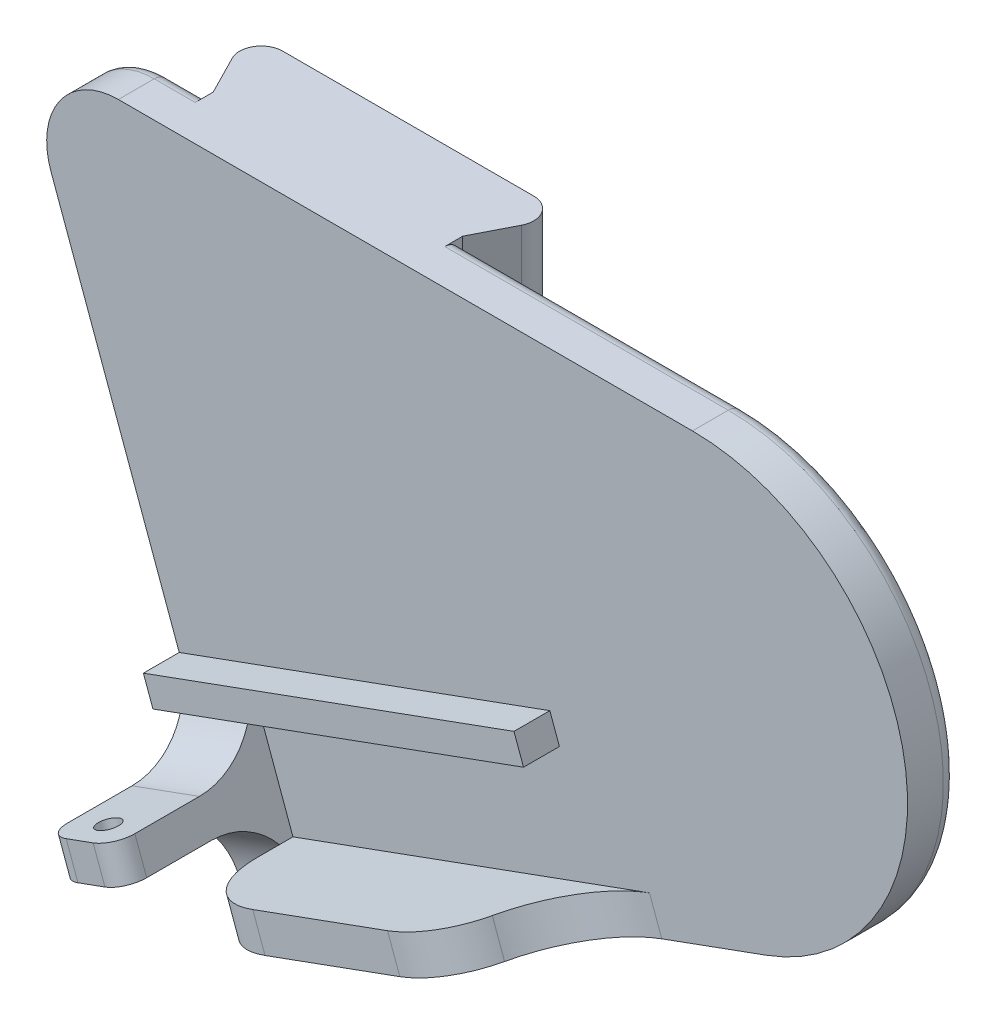
SolidWorks part; units mm, degrees
ref_plane "Alzado" through (0, 0, 0) normal (0, 0, 1) x (1, 0, 0)
ref_plane "Planta" through (0, 0, 0) normal (0, 1, 0) x (1, 0, 0)
ref_plane "Vista lateral" through (0, 0, 0) normal (1, 0, 0) x (0, 0, -1)
sketch "Croquis1" plane through (0, 0, 0) normal (0, 1, 0) x (1, 0, 0)
  line L0 (-20.1738, -4.3634) -> (-17.4, -9.8)
  line L1 (17.4, -9.8) -> (-17.4, -9.8) construction
  line L3 (17.5015, 0) -> (-17.5015, 0)
  line L5 (20.1738, -4.3634) -> (17.4, -9.8)
  line L8 (-17.4, -9.8) -> (-17.4, -10.3)
  line L9 (-17.4, -10.3) -> (17.4, -10.3)
  line L10 (17.4, -9.8) -> (17.4, -10.3)
  arc A0 (20.1738, -4.3634) -> (17.5015, 0) centre (17.5015, -3) ccw
  arc A1 (-17.5015, 0) -> (-20.1738, -4.3634) centre (-17.5015, -3) ccw
  point P0 (0, 0)
  point P2 (0, -9.8)
  point P6 (0, 0)
  point P8 (22.4, 0)
  point P13 (-22.4, 0)
  dimension "D4" = 3
  dimension "D1" = 9.8
  dimension "D2" = 44.8
  dimension "D3" = 5
  dimension "D5" = 0.5
extrude "Saliente-Extruir1" add sketch "Croquis1" along normal blind 18
sketch "Croquis2" plane through (0, 0, 10.3) normal (0, 0, 1) x (1, 0, 0)
  line L0 (-17.4, 18) -> (-23.1185, 18)
  line L1 (-32.5154, 4.5798) -> (-6.4625, -67)
  line L2 (-6.4625, -67) -> (67.1952, -40.1908)
  line L3 (-17.4, 18) -> (56.9346, 18)
  arc A0 (67.1952, -40.1908) -> (56.9346, 18) centre (56.9346, -12) ccw
  arc A1 (-23.1185, 18) -> (-32.5154, 4.5798) centre (-23.1185, 8) ccw
  point P9 (-37.4, 18)
  dimension "D2" = 30
  dimension "D5" = 10
  dimension "D1" = 20
  dimension "D3" = 85
  dimension "D4" = 20
extrude "Saliente-Extruir2" add sketch "Croquis2" along normal blind 7
sketch "Croquis4" plane through (-27.2399, -9.9145, 0) normal (-0.9397, -0.342, 0) x (0, 0, 1)
  line L0 (17.3, 15.4245) -> (17.3, -60.7491) construction
  line L1 (17.3, -46.8491) -> (39.3, -46.8491)
  line L2 (17.3, -46.8491) -> (17.3, -51.6491)
  line L3 (17.3, -51.6491) -> (39.3, -51.6491)
  line L4 (39.3, -46.8491) -> (39.3, -51.6491)
  dimension "D1" = 22
  dimension "D2" = 4.8
  dimension "D3" = 9.1
extrude "Saliente-Extruir3" add sketch "Croquis4" against normal blind 10
fillet "Redondeo1" radius 10 2 edges at (-6.5181, -52.2282, 17.3) (-4.8765, -56.7387, 17.3)
fillet "Redondeo2" radius 3 2 edges at (-0.9988, -52.7733, 39.3) (-10.3958, -56.1935, 39.3)
sketch "Croquis5" plane through (17.665, -48.5343, 0) normal (0.342, -0.9397, 0) x (0.9397, 0.342, 0)
  line L0 (-21.9881, 39.3) -> (-25.9881, 39.3) construction
  circle A0 centre (-23.9881, 35.3) radius 1.5
  point P4 (-23.9881, 39.3)
  dimension "D2" = 3
  dimension "D1" = 4
extrude "Cortar-Extruir1" cut sketch "Croquis5" against normal through all
sketch "Croquis6" plane through (20.7774, -57.0855, 0) normal (0.342, -0.9397, 0) x (0.9397, 0.342, 0)
  line L1 (-18.9881, 17.3) -> (21.0119, 17.3)
  line L2 (-18.9881, 17.3) -> (-18.9881, 32.3)
  line L3 (-18.9881, 32.3) -> (21.0119, 32.3)
  line L4 (21.0119, 17.3) -> (21.0119, 32.3)
  dimension "D1" = 40
  dimension "D2" = 15
extrude "Saliente-Extruir4" add sketch "Croquis6" against normal blind 5
fillet "Redondeo3" radius 10 2 edges at (2.0793, -61.2306, 32.3) (39.6671, -47.5498, 32.3)
fillet "Redondeo4" radius 15 1 edges at (39.6671, -47.5498, 17.3)
fillet "Redondeo5" radius 2 6 edges at (37.1673, 18, 10.3) (86.4788, -6.7906, 10.3) (-20.2593, 18, 10.3) (-31.31, 13.7358, 10.3) (30.3663, -53.5954, 10.3) (-19.489, -31.2101, 10.3)
sketch "Croquis7" plane through (0, 0, 17.3) normal (0, 0, 1) x (1, 0, 0)
  line L0 (-14.6368, -44.5413) -> (37.0463, -25.7302)
  line L1 (-14.6368, -44.5413) -> (-5.2399, -41.1211) construction
  line L2 (37.0463, -25.7302) -> (38.3802, -29.395)
  line L3 (38.3802, -29.395) -> (-13.3029, -48.2061)
  line L5 (1.2243, -58.8813) -> (50.9461, -40.7841) construction
  line L7 (-14.6368, -44.5413) -> (-11.2166, -53.9383) construction
  line L8 (-14.6368, -44.5413) -> (-13.3029, -48.2061)
  dimension "D1" = 55
  dimension "D2" = 15
extrude "Saliente-Extruir5" add sketch "Croquis7" along normal blind 5
